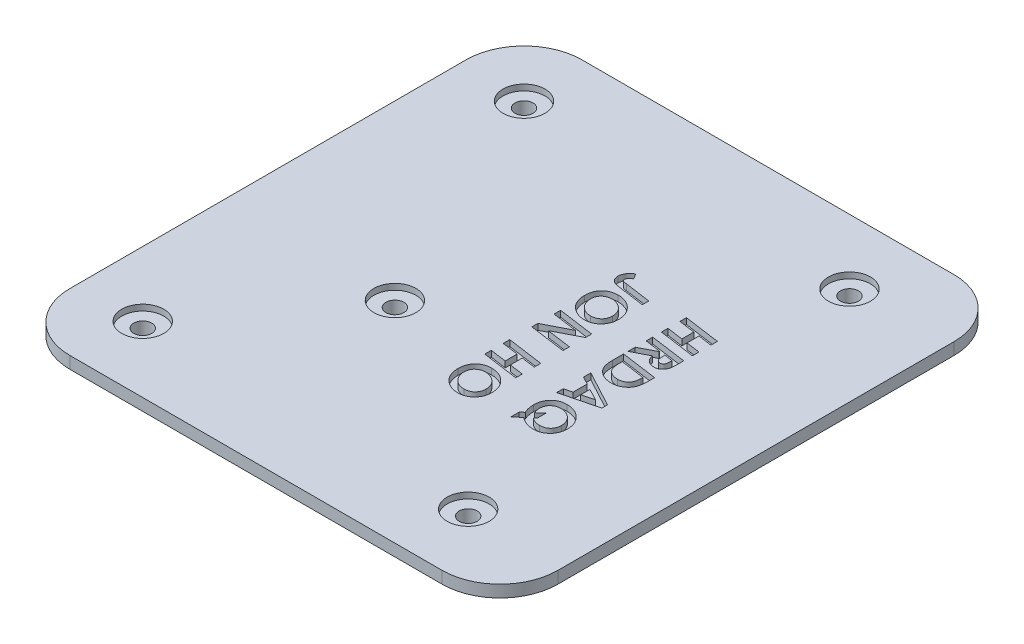
SolidWorks part; units mm, degrees
ref_plane "Front Plane" through (0, 0, 0) normal (0, 0, 1) x (1, 0, 0)
ref_plane "Top Plane" through (0, 0, 0) normal (0, 1, 0) x (1, 0, 0)
ref_plane "Right Plane" through (0, 0, 0) normal (1, 0, 0) x (0, 0, -1)
sketch "HRDAQ_PCB_Sketch" plane through (0, 0, 0) normal (0, 1, 0) x (1, 0, 0)
  line L0 (4, -38.85) -> (13, -38.85)
  line L1 (-27.1, -31.75) -> (27.1, -31.75) construction
  line L2 (-27.1, -31.75) -> (-27.1, 31.75) construction
  line L3 (-27.1, 31.75) -> (27.1, 31.75) construction
  line L4 (27.1, -31.75) -> (27.1, 31.75) construction
  line L5 (-27.1, -31.75) -> (27.1, 31.75) construction
  line L6 (-27.1, 31.75) -> (27.1, -31.75) construction
  line L7 (-28.25, 35.9) -> (33.75, 35.9)
  line L8 (-31.25, 32.9) -> (-31.25, -33.1)
  line L9 (-28.25, -36.1) -> (1.25, -36.1)
  line L10 (36.75, 32.9) -> (36.75, -33.1)
  line L11 (4, -38.85) -> (1.25, -36.1)
  line L12 (13, -38.85) -> (15.75, -36.1)
  line L13 (15.75, -36.1) -> (33.75, -36.1)
  circle A0 centre (-27.1, 31.75) radius 1.5
  circle A1 centre (27.1, 31.75) radius 1.5
  circle A2 centre (27.1, -31.75) radius 1.5
  circle A3 centre (-27.1, -31.75) radius 1.5
  circle A4 centre (-9.1, -7.75) radius 1.5
  arc A5 (-28.25, -36.1) -> (-31.25, -33.1) centre (-28.25, -33.1) cw
  arc A6 (33.75, -36.1) -> (36.75, -33.1) centre (33.75, -33.1) ccw
  arc A7 (36.75, 32.9) -> (33.75, 35.9) centre (33.75, 32.9) ccw
  arc A8 (-28.25, 35.9) -> (-31.25, 32.9) centre (-28.25, 32.9) ccw
  point P0 (0, 0)
  point P12 (8.5, -38.85)
  point P20 (8.5, -38.85)
  point P26 (36.75, -36.1)
  point P29 (36.75, 35.9)
  point P32 (-31.25, 35.9)
  dimension "D3" = 3
  dimension "D14" = 3
  dimension "D1" = 54.2
  dimension "D2" = 63.5
  dimension "D4" = 24
  dimension "D5" = 18
  dimension "D6" = 35.6
  dimension "D7" = 7.1
  dimension "D8" = 4.15
  dimension "D9" = 9
  dimension "D10" = 4.15
  dimension "D11" = 72
  dimension "D12" = 68
  dimension "D13" = 135
sketch "HRDAQ_PCB_Base_Sketch" plane through (0, 0, 0) normal (0, 1, 0) x (1, 0, 0)
  line L8 (-28.25, -40.1) -> (33.75, -40.1)
  line L9 (-37.89, 32.9) -> (-37.89, -33.1)
  line L10 (-28.25, -42.74) -> (33.75, -42.74)
  line L11 (43.39, -33.1) -> (43.39, 32.9)
  line L12 (33.75, 42.54) -> (-28.25, 42.54)
  line L16 (-35.25, 32.9) -> (-35.25, -33.1)
  line L17 (-28.25, -40.1) -> (-0.4069, -40.1)
  line L18 (-0.4069, -40.1) -> (2.3431, -42.85)
  line L19 (2.3431, -42.85) -> (14.6569, -42.85)
  line L20 (14.6569, -42.85) -> (17.4069, -40.1)
  line L21 (17.4069, -40.1) -> (33.75, -40.1)
  line L22 (40.75, -33.1) -> (40.75, 32.9)
  line L23 (33.75, 39.9) -> (-28.25, 39.9)
  line L24 (-35.25, 32.9) -> (-35.25, -33.1)
  line L30 (40.75, -33.1) -> (40.75, 32.9)
  line L31 (33.75, 39.9) -> (-28.25, 39.9)
  arc A4 (-37.89, -33.1) -> (-28.25, -42.74) centre (-28.25, -33.1) ccw
  arc A5 (33.75, -42.74) -> (43.39, -33.1) centre (33.75, -33.1) ccw
  arc A6 (43.39, 32.9) -> (33.75, 42.54) centre (33.75, 32.9) ccw
  arc A7 (-28.25, 42.54) -> (-37.89, 32.9) centre (-28.25, 32.9) ccw
  arc A8 (-35.25, -33.1) -> (-28.25, -40.1) centre (-28.25, -33.1) ccw
  arc A9 (33.75, -40.1) -> (40.75, -33.1) centre (33.75, -33.1) ccw
  arc A10 (40.75, 32.9) -> (33.75, 39.9) centre (33.75, 32.9) ccw
  arc A11 (-28.25, 39.9) -> (-35.25, 32.9) centre (-28.25, 32.9) ccw
  arc A12 (-35.25, -33.1) -> (-28.25, -40.1) centre (-28.25, -33.1) ccw
  arc A13 (33.75, -40.1) -> (40.75, -33.1) centre (33.75, -33.1) ccw
  arc A14 (40.75, 32.9) -> (33.75, 39.9) centre (33.75, 32.9) ccw
  arc A15 (-28.25, 39.9) -> (-35.25, 32.9) centre (-28.25, 32.9) ccw
  dimension "D1" = 4
  dimension "D2" = 2.64
sketch "Sketch1" plane through (0, 0, 0) normal (0, 1, 0) x (1, 0, 0)
  line L0 (-28.25, -42.74) -> (33.75, -42.74) construction
  line L1 (43.39, -33.1) -> (43.39, 32.9) construction
  line L2 (33.75, 42.54) -> (-28.25, 42.54) construction
  line L3 (-37.89, 32.9) -> (-37.89, -33.1) construction
  line L4 (-28.25, -42.74) -> (33.75, -42.74)
  line L5 (43.39, -33.1) -> (43.39, 32.9)
  line L6 (33.75, 42.54) -> (-28.25, 42.54)
  line L7 (-37.89, 32.9) -> (-37.89, -33.1)
  arc A0 (-37.89, -33.1) -> (-28.25, -42.74) centre (-28.25, -33.1) ccw construction
  arc A1 (33.75, -42.74) -> (43.39, -33.1) centre (33.75, -33.1) ccw construction
  arc A2 (43.39, 32.9) -> (33.75, 42.54) centre (33.75, 32.9) ccw construction
  arc A3 (-28.25, 42.54) -> (-37.89, 32.9) centre (-28.25, 32.9) ccw construction
  arc A4 (-37.89, -33.1) -> (-28.25, -42.74) centre (-28.25, -33.1) ccw
  arc A5 (33.75, -42.74) -> (43.39, -33.1) centre (33.75, -33.1) ccw
  arc A6 (43.39, 32.9) -> (33.75, 42.54) centre (33.75, 32.9) ccw
  arc A7 (-28.25, 42.54) -> (-37.89, 32.9) centre (-28.25, 32.9) ccw
  circle A8 centre (27.1, -31.75) radius 1.5 construction
  circle A9 centre (-27.1, -31.75) radius 1.5 construction
  circle A10 centre (-9.1, -7.75) radius 1.5 construction
  circle A11 centre (27.1, 31.75) radius 1.5 construction
  circle A12 centre (-27.1, 31.75) radius 1.5 construction
  circle A13 centre (27.1, -31.75) radius 1.5
  circle A14 centre (-27.1, -31.75) radius 1.5
  circle A15 centre (-9.1, -7.75) radius 1.5
  circle A16 centre (27.1, 31.75) radius 1.5
  circle A17 centre (-27.1, 31.75) radius 1.5
extrude "Base_Extrude" add sketch "Sketch1" along normal blind 2
sketch "Sketch2" plane through (0, 0, 0) normal (0, -1, 0) x (1, 0, 0)
  circle A0 centre (-27.1, 31.75) radius 2.82
  circle A1 centre (-9.1, 7.75) radius 2.82
  circle A2 centre (27.1, 31.75) radius 2.82
  circle A3 centre (27.1, -31.75) radius 2.82
  circle A4 centre (-27.1, -31.75) radius 2.82
  circle A5 centre (-27.1, 31.75) radius 1.5
  circle A6 centre (-9.1, 7.75) radius 1.5
  circle A7 centre (27.1, 31.75) radius 1.5
  circle A8 centre (27.1, -31.75) radius 1.5
  circle A9 centre (-27.1, -31.75) radius 1.5
  circle A10 centre (-27.1, 31.75) radius 1.5 construction
  dimension "D1" = 5.64
extrude "Boss-Extrude1" add sketch "Sketch2" along normal blind 6.45
sketch "Sketch3" plane through (0, 0, 0) normal (0, -1, 0) x (1, 0, 0)
  line L0 (33.75, -39.9) -> (-28.25, -39.9) construction
  line L1 (40.75, 33.1) -> (40.75, -32.9) construction
  line L2 (-28.25, 40.1) -> (33.75, 40.1) construction
  line L3 (-35.25, -32.9) -> (-35.25, 33.1) construction
  line L4 (33.75, -39.9) -> (-28.25, -39.9) construction
  line L5 (40.75, 33.1) -> (40.75, -32.9) construction
  line L6 (-28.25, 40.1) -> (33.75, 40.1) construction
  line L7 (-35.25, -32.9) -> (-35.25, 33.1) construction
  line L8 (-34.75, -32.9) -> (-34.75, 33.1)
  line L9 (33.75, -39.4) -> (-28.25, -39.4)
  line L10 (40.25, 33.1) -> (40.25, -32.9)
  line L11 (-28.25, 39.6) -> (33.75, 39.6)
  line L12 (-32.11, -32.9) -> (-32.11, 33.1)
  line L13 (33.75, -36.76) -> (-28.25, -36.76)
  line L14 (37.61, 33.1) -> (37.61, -32.9)
  line L15 (-28.25, 36.96) -> (33.75, 36.96)
  arc A0 (-35.25, -32.9) -> (-28.25, -39.9) centre (-28.25, -32.9) ccw construction
  arc A1 (33.75, -39.9) -> (40.75, -32.9) centre (33.75, -32.9) ccw construction
  arc A2 (40.75, 33.1) -> (33.75, 40.1) centre (33.75, 33.1) ccw construction
  arc A3 (-28.25, 40.1) -> (-35.25, 33.1) centre (-28.25, 33.1) ccw construction
  arc A4 (-35.25, -32.9) -> (-28.25, -39.9) centre (-28.25, -32.9) ccw construction
  arc A5 (33.75, -39.9) -> (40.75, -32.9) centre (33.75, -32.9) ccw construction
  arc A6 (40.75, 33.1) -> (33.75, 40.1) centre (33.75, 33.1) ccw construction
  arc A7 (-28.25, 40.1) -> (-35.25, 33.1) centre (-28.25, 33.1) ccw construction
  arc A8 (-28.25, 39.6) -> (-34.75, 33.1) centre (-28.25, 33.1) ccw
  arc A9 (-34.75, -32.9) -> (-28.25, -39.4) centre (-28.25, -32.9) ccw
  arc A10 (33.75, -39.4) -> (40.25, -32.9) centre (33.75, -32.9) ccw
  arc A11 (40.25, 33.1) -> (33.75, 39.6) centre (33.75, 33.1) ccw
  arc A12 (-28.25, 36.96) -> (-32.11, 33.1) centre (-28.25, 33.1) ccw
  arc A13 (-32.11, -32.9) -> (-28.25, -36.76) centre (-28.25, -32.9) ccw
  arc A14 (33.75, -36.76) -> (37.61, -32.9) centre (33.75, -32.9) ccw
  arc A15 (37.61, 33.1) -> (33.75, 36.96) centre (33.75, 33.1) ccw
  dimension "D2" = 2.64
  dimension "D1" = 0.5
extrude "Boss-Extrude2" add sketch "Sketch3" along normal blind 2
chamfer "Chamfer1" distance 2 angle 45 8 edges at (37.61, 0, 0.1) (36.4794, 0, 35.8294) (36.4794, 0, -35.6294) (2.75, 0, 36.96) (2.75, 0, -36.76) (-30.9794, 0, 35.8294) (-30.9794, 0, -35.6294) (-32.11, 0, 0.1)
sketch "Sketch4" plane through (0, 2, 0) normal (0, 1, 0) x (1, 0, 0)
  circle A0 centre (-27.1, -31.75) radius 3.5
  circle A1 centre (-27.1, 31.75) radius 3.5
  circle A2 centre (-9.1, -7.75) radius 3.5
  circle A3 centre (27.1, -31.75) radius 3.5
  circle A4 centre (27.1, 31.75) radius 3.5
  dimension "D1" = 7
extrude "Cut-Extrude1" cut sketch "Sketch4" against normal blind 1
sketch "Sketch5" plane through (0, 2, 0) normal (0, 1, 0) x (1, 0, 0)
  line L0 (17.6468, -42.74) -> (17.6468, 42.54) construction
  line L1 (33.75, 42.54) -> (-28.25, 42.54) construction
  line L2 (-28.25, -42.74) -> (33.75, -42.74) construction
  text T0 "<b><i>HRDAQ</i></b>\r\n<b><i>JON HO</i></b>" font "Century Gothic" height 6
  point P3 (0, 0)
  point P6 (0, 0)
extrude "Cut-Extrude2" cut sketch "Sketch5" against normal blind 1
equation "\"Wall_Thickness\"= 2.64mm"
equation "\"D2@HRDAQ_PCB_Base_Sketch\" = \"Wall_Thickness\""
equation "\"Base_Thickness\"= 2mm"
equation "\"D1@Base_Extrude\" = \"Base_Thickness\""
equation "\"Peg_Height\"=6.45"
equation "\"D1@Boss-Extrude1\"=\"Peg_Height\""
equation "\"D2@Sketch3\"=\"Wall_Thickness\""
